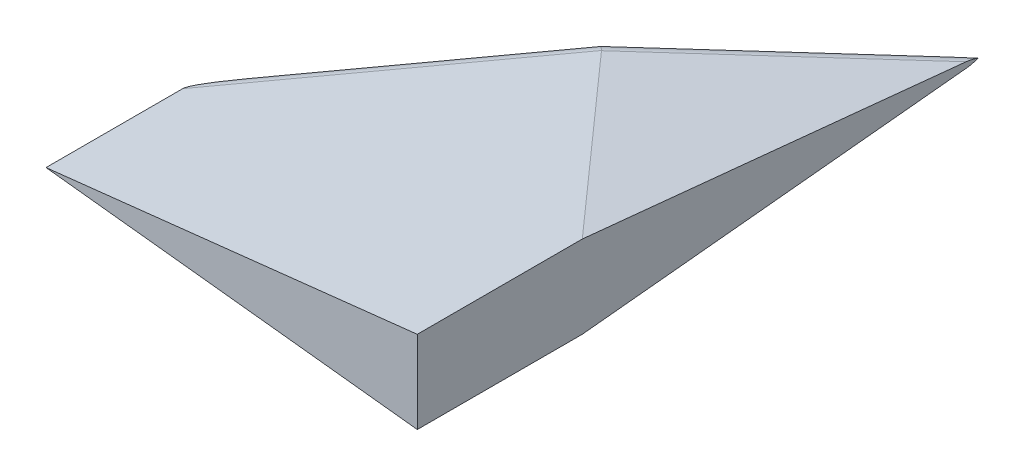
SolidWorks part; units mm, degrees
ref_plane "Front Plane" through (0, 0, 0) normal (0, 0, 1) x (1, 0, 0)
ref_plane "Top Plane" through (0, 0, 0) normal (0, 1, 0) x (1, 0, 0)
ref_plane "Right Plane" through (0, 0, 0) normal (1, 0, 0) x (0, 0, -1)
sketch "Sketch1" plane through (0, 0, 0) normal (0, 1, 0) x (1, 0, 0)
  line L0 (-22.5, -35) -> (-22.5, -15)
  line L2 (-22.5, -15) -> (-22.5, -35)
  line L3 (-22.5, -35) -> (22.5, -35)
  line L4 (22.5, 35) -> (22.5, -35)
  line L5 (-3.75, 5.8333) -> (22.5, -35) construction
  line L6 (-22.5, -35) -> (22.5, 35) construction
  line L7 (-22.5, -15) -> (22.5, 35)
  point P0 (0, 0)
  dimension "D1" = 70
  dimension "D2" = 45
  dimension "D3" = 20
extrude "Boss-Extrude1" add sketch "Sketch1" along normal blind 10 contours L7 L0 L3 L4 region at (4.1667, 0, 10.1852)
sketch "Sketch2" plane through (22.5, 0, 0) normal (1, 0, 0) x (0, 0, -1)
  line L0 (35, 0) -> (-35, 0) construction
  line L1 (-35, 10) -> (-15, 10)
  line L2 (-35, 10) -> (-35, 0)
  line L3 (-35, 0) -> (-15, 0)
  line L4 (-15, 10) -> (-15, 0)
  line L5 (35, 10) -> (35, 0) construction
  line L6 (-15, 10) -> (35, 10)
  line L7 (-15, 10) -> (-15, 5)
  line L8 (-15, 5) -> (35, 5)
  line L9 (35, 10) -> (35, 5)
  line L10 (-15, 10) -> (35, 5)
  line L11 (-15, 0) -> (35, 5)
  line M6 (-35, 0) -> (35, 0)
  line M7 (35, 0) -> (35, 10)
  line M8 (35, 10) -> (-35, 10)
  dimension "D1" = 20
  dimension "D2" = 5
extrude "Cut-Extrude1" cut sketch "Sketch2" against normal through all contours L11 M6 M7 | L10 M8 M7 region at (22.5, 8.3333, -18.3333) region at (22.5, 1.6667, -18.3333)
sketch "Sketch3" plane through (0, 0, 35) normal (0, 0, 1) x (1, 0, 0)
  line L0 (-22.5, 10) -> (-22.5, 0) construction
  line L1 (22.5, 0) -> (-22.5, 0)
  line L2 (22.5, 0) -> (22.5, 5)
  line L3 (22.5, 5) -> (-22.5, 5)
  line L4 (-22.5, 0) -> (-22.5, 5)
  line L5 (22.5, 0) -> (-22.5, 5)
  line L6 (22.5, 10) -> (-22.5, 5)
  line M6 (-22.5, 0) -> (22.5, 0)
  line M8 (22.5, 10) -> (-22.5, 10)
  line M9 (-22.5, 10) -> (-22.5, 0)
  dimension "D1" = 5
extrude "Cut-Extrude2" cut sketch "Sketch3" against normal through all contours L6 M8 M9 | L5 M6 M9 region at (-7.5, 8.3333, 35) region at (-7.5, 1.6667, 35)
fillet "Fillet1" radius 2.5 4 edges at (11.25, 6.25, -22.5) (-11.25, 6.25, 2.5) (-11.25, 3.75, 2.5) (11.25, 3.75, -22.5)
